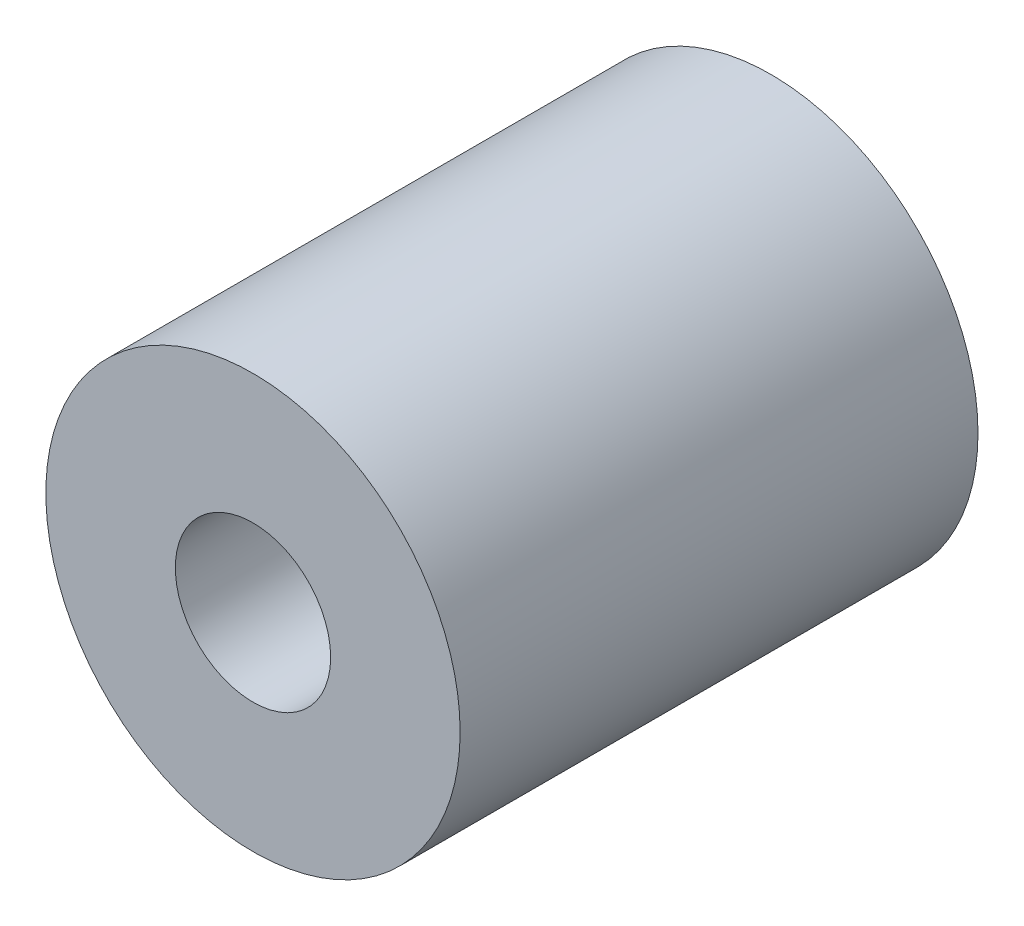
SolidWorks part; units mm, degrees
ref_plane "Ebene vorne" through (0, 0, 0) normal (0, 0, 1) x (1, 0, 0)
ref_plane "Ebene oben" through (0, 0, 0) normal (0, 1, 0) x (1, 0, 0)
ref_plane "Ebene rechts" through (0, 0, 0) normal (1, 0, 0) x (0, 0, -1)
sketch "Skizze1" plane through (0, 0, 0) normal (0, 0, 1) x (1, 0, 0)
  circle A0 centre (0, 0) radius 8
  dimension "D1" = 16
extrude "Aufsatz-Linear austragen1" add sketch "Skizze1" along normal blind 10 and the other way blind 10
hole_wizard "Ø6.0 (6) Durchmesser Bohrung1" positions "Skizze2" profile "Skizze3" hole size "Ø6.0" standard "DIN"
sketch "Skizze2" plane through (0, 0, 10) normal (0, 0, 1) x (1, 0, 0)
  point P0 (0, 0)
sketch "Skizze3" plane through (0, 0, 10) normal (1, 0, 0) x (0, -1, 0)
  line L0 (0, 0) -> (0, 10)
  line L1 (0, 10) -> (3, 8.1974)
  line L2 (3, 8.1974) -> (3, 0)
  line L5 (3, 0) -> (0, 0)
  line L10 (0, 10) -> (-3, 8.1974) construction
  line L11 (0, -6.35) -> (0, 107.95) construction
  dimension "Bohrerdurchmesser" = 6
  dimension "Bohrungstiefe" = 10
  dimension "Spitzenwinkel" = 118
hole_wizard "Ø5.0 (5) Durchmesser Bohrung5" positions "Skizze4" profile "Skizze5" hole size "Ø5.0" standard "DIN"
sketch "Skizze4" plane through (0, 0, -10) normal (0, 0, -1) x (-1, 0, 0)
  point P0 (0, 0)
sketch "Skizze5" plane through (0, 0, -10) normal (1, 0, 0) x (0, 1, 0)
  line L0 (0, 0) -> (0, 20)
  line L1 (0, 20) -> (2.5, 18.4978)
  line L2 (2.5, 18.4978) -> (2.5, 0)
  line L5 (2.5, 0) -> (0, 0)
  line L10 (0, 20) -> (-2.5, 18.4978) construction
  line L11 (0, -6.35) -> (0, 107.95) construction
  dimension "Bohrerdurchmesser" = 5
  dimension "Bohrungstiefe" = 20
  dimension "Spitzenwinkel" = 118
